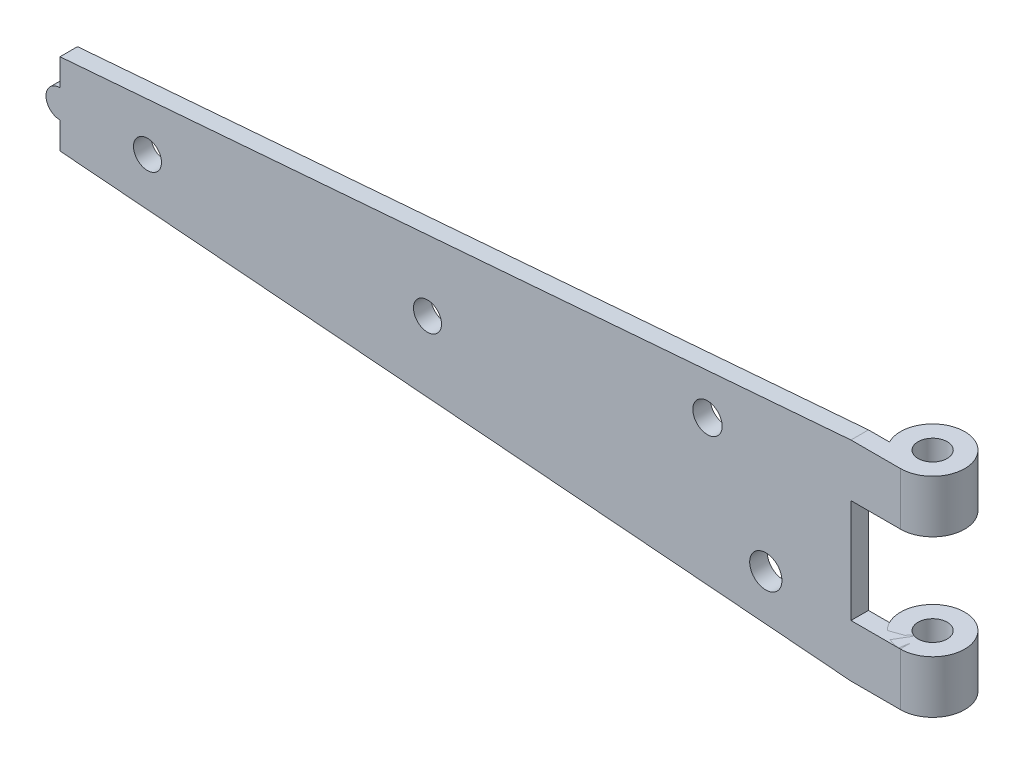
SolidWorks part; units mm, degrees
ref_plane "Front Plane" through (0, 0, 0) normal (0, 0, 1) x (1, 0, 0)
ref_plane "Top Plane" through (0, 0, 0) normal (0, 1, 0) x (1, 0, 0)
ref_plane "Right Plane" through (0, 0, 0) normal (1, 0, 0) x (0, 0, -1)
sketch "Sketch1" plane through (0, 0, 0) normal (0, 0, 1) x (1, 0, 0)
  line L0 (0, 0) -> (-135.6, 10.9)
  line L1 (-135.6, 10.9) -> (-135.6, 15.5)
  line L2 (-135.6, 24.9) -> (0, 35.8)
  line L4 (0, 0) -> (-135.6, 0) construction
  line L5 (-135.6, 0) -> (-135.6, 15.5) construction
  line L6 (-135.6, 35.8) -> (0, 35.8) construction
  line L7 (-24.6, 26.8) -> (-72.6, 17.9) construction
  line L12 (-135.6, 20.3) -> (-135.6, 24.9)
  line L13 (-135.6, 20.3) -> (-135.6, 35.8) construction
  line L15 (0, 26.8) -> (0, 9)
  line L16 (0, 35.8) -> (8.45, 35.8)
  line L18 (0, 26.8) -> (8.45, 26.8)
  line L19 (8.45, 35.8) -> (8.45, 26.8)
  line L20 (0, 0) -> (8.45, 0)
  line L22 (0, 9) -> (8.45, 9)
  line L23 (8.45, 0) -> (8.45, 9)
  arc A0 (-135.6, 20.3) -> (-135.6, 15.5) centre (-135.6, 17.9) ccw
  circle A1 centre (-120.6, 17.9) radius 2.4
  circle A2 centre (-72.6, 17.9) radius 2.4
  circle A3 centre (-24.6, 26.8) radius 2.515
  circle A4 centre (-14.6, 9) radius 2.764
  dimension "D4" = 4.8
  dimension "D5" = 4.8
  dimension "D6" = 4.8
  dimension "D1" = 10.9
  dimension "D2" = 10.9
  dimension "D3" = 14
  dimension "D11" = 15
  dimension "D12" = 48
  dimension "D13" = 48
  dimension "D14" = 10
  dimension "D15" = 9
  dimension "D16" = 9
extrude "Boss-Extrude1" add sketch "Sketch1" along normal blind 3
sketch "Sketch2" plane through (0, 0, 0) normal (0, 1, 0) x (1, 0, 0)
  line L0 (-138, 0) -> (-138, -3) construction
  line L2 (8.45, -3) -> (0, -3) construction
  circle A0 centre (8.5, 2.5) radius 5.5
  dimension "D1" = 146.5
  dimension "D2" = 11
  dimension "D3" = 5.5
extrude "Boss-Extrude2" add sketch "Sketch2" along normal up to surface (9 mm away) from surface separate body up to face at (4.225, 9, 1.5) starting at face at (4.225, 0, 1.5)
sketch "Sketch4" plane through (0, 0, 0) normal (0, 1, 0) x (1, 0, 0)
  circle A0 centre (8.5, 2.5) radius 2.5
  dimension "D1" = 5
extrude "Boss-Extrude3" add sketch "Sketch2<2>" along normal up to surface (35.8 mm away) from surface up to face at (4.225, 35.8, 1.5) starting at face at (4.225, 26.8, 1.5)
sketch "Sketch2<2>" plane through (0, 0, 0) normal (0, 1, 0) x (1, 0, 0) same geometry as "Sketch2"
extrude "Cut-Extrude1" cut sketch "Sketch4" along normal through all
